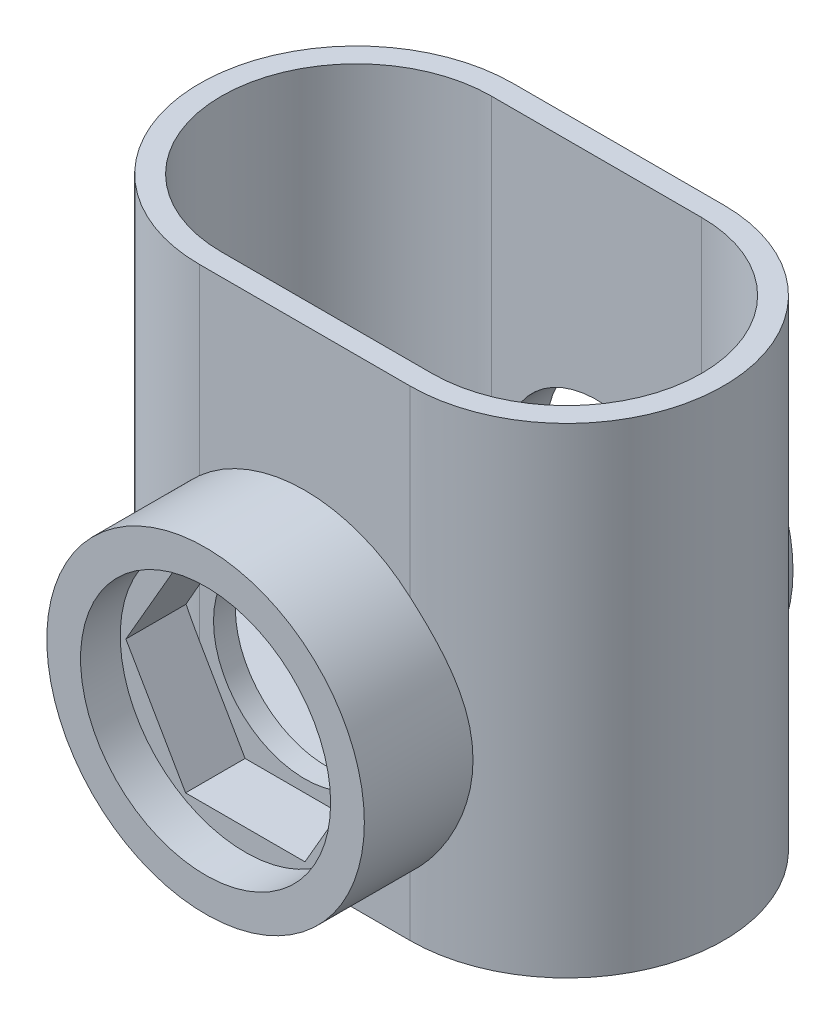
SolidWorks part; units mm, degrees
ref_plane "前基準面" through (0, 0, 0) normal (0, 0, 1) x (1, 0, 0)
ref_plane "上基準面" through (0, 0, 0) normal (0, 1, 0) x (1, 0, 0)
ref_plane "右基準面" through (0, 0, 0) normal (1, 0, 0) x (0, 0, -1)
sketch "草圖1" plane through (0, 0, 0) normal (0, 1, 0) x (1, 0, 0)
  line L0 (0, 0) -> (10.6, 0) construction
  line L3 (0, 7.9) -> (10.6, 7.9)
  line L4 (0, -7.9) -> (10.6, -7.9)
  arc A2 (0, 7.9) -> (0, -7.9) centre (0, 0) ccw
  arc A3 (10.6, -7.9) -> (10.6, 7.9) centre (10.6, 0) ccw
  point P3 (5.3, 0)
  dimension "D1" = 26.4
  dimension "D2" = 15.8
extrude "填料-伸長1" add sketch "草圖1" along normal blind 24.2
ref_plane "平面1" through (0, 0, 12.9) normal (0, 0, 1) x (1, 0, 0)
sketch "草圖2" plane through (0, 0, 12.9) normal (0, 0, 1) x (1, 0, 0)
  line L0 (5.3, 24.2) -> (5.3, -2.0344) construction
  line L1 (0, 24.2) -> (10.6, 24.2) construction
  line L2 (10.6, 0) -> (18.5, 0) construction
  line L3 (0, 0) -> (10.6, 0) construction
  line L4 (8.308, 14.21) -> (2.292, 14.21)
  line L5 (2.292, 14.21) -> (-0.716, 9)
  line L6 (-0.716, 9) -> (2.292, 3.79)
  line L7 (2.292, 3.79) -> (8.308, 3.79)
  line L8 (8.308, 3.79) -> (11.316, 9)
  line L9 (11.316, 9) -> (8.308, 14.21)
  circle A0 centre (5.3, 9) radius 8
  circle A2 centre (5.3, 9) radius 5.21 construction
  dimension "D1" = 16
  dimension "D3" = 10.42
  dimension "D2" = 9
extrude "填料-伸長2" add sketch "草圖2" against normal up to next
sketch "草圖7" plane through (0, 0, 12.9) normal (0, 0, 1) x (1, 0, 0)
  circle A0 centre (5.3, 9) radius 6.3
  dimension "D1" = 12.6
extrude "除料-伸長5" cut sketch "草圖7" against normal blind 2
sketch "草圖8" plane through (0, 0, -7.9) normal (0, 0, -1) x (-1, 0, 0)
  circle A0 centre (-5.3, 9) radius 4.6
  circle A1 centre (-5.3, 9) radius 7.8
  dimension "D1" = 9.2
  dimension "D2" = 15.6
extrude "除料-伸長6" cut sketch "草圖8" against normal through all contours A0 region at (5.3, 9, -7.9)
extrude "填料-伸長3" add sketch "草圖8<3>" along normal blind 1
sketch "草圖8<3>" plane through (0, 0, -7.9) normal (0, 0, -1) x (-1, 0, 0) same geometry as "草圖8"
sketch "草圖9" plane through (0, 24.2, 0) normal (0, 1, 0) x (1, 0, 0)
  line L0 (0, -7.9) -> (10.6, -7.9) construction
  line L5 (10.6, 7.9) -> (0, 7.9) construction
  line L6 (0, -7.9) -> (10.6, -7.9)
  line L7 (10.6, 7.9) -> (0, 7.9)
  line L8 (10.6, 6.8) -> (0, 6.8)
  line L9 (0, -6.8) -> (10.6, -6.8)
  arc A5 (10.6, -7.9) -> (10.6, 7.9) centre (10.6, 0) ccw construction
  arc A6 (0, 7.9) -> (0, -7.9) centre (0, 0) ccw construction
  arc A7 (10.6, -7.9) -> (10.6, 7.9) centre (10.6, 0) ccw
  arc A8 (0, 7.9) -> (0, -7.9) centre (0, 0) ccw
  arc A9 (10.6, -6.8) -> (10.6, 6.8) centre (10.6, 0) ccw
  arc A10 (0, 6.8) -> (0, -6.8) centre (0, 0) ccw
  dimension "D1" = 1.1
extrude "除料-伸長7" cut sketch "草圖9" against normal blind 22.6 contours L8 A10 L9 A9 region at (5.3, 24.2, 0)
